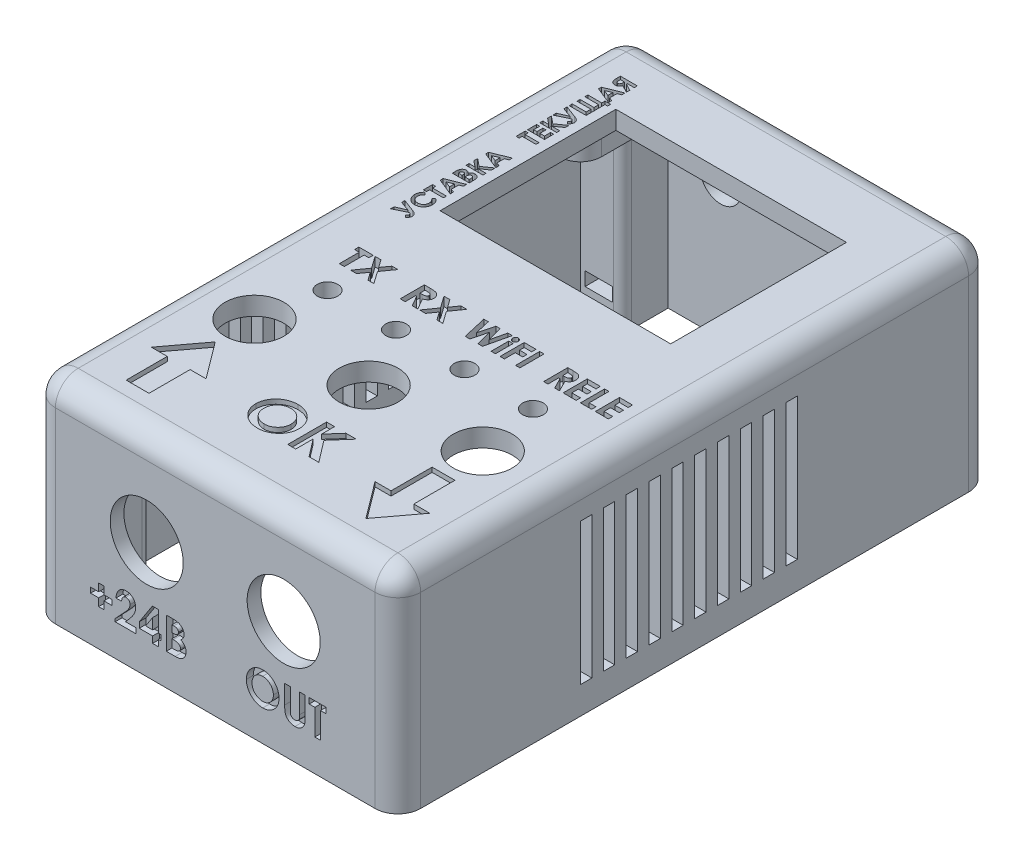
SolidWorks part; units mm, degrees
ref_plane "Спереди" through (0, 0, 0) normal (0, 0, 1) x (1, 0, 0)
ref_plane "Сверху" through (0, 0, 0) normal (0, 1, 0) x (1, 0, 0)
ref_plane "Справа" through (0, 0, 0) normal (1, 0, 0) x (0, 0, -1)
sketch "Эскиз1" plane through (0, 0, 0) normal (0, 1, 0) x (1, 0, 0)
  line L0 (-1000, 0) -> (49000, 0) construction
  line L1 (0, -1000) -> (0, 49000) construction
  line L2 (-1000, -65) -> (49000, -65) construction
  line L3 (-1000, 65) -> (49000, 65) construction
  line L4 (40, -1000) -> (40, 49000) construction
  line L5 (-40, -1000) -> (-40, 49000) construction
  line L6 (-40, 65) -> (40, 65)
  line L7 (40, 65) -> (40, -65)
  line L8 (40, -65) -> (-40, -65)
  line L9 (-40, -65) -> (-40, 65)
extrude "Бобышка-Вытянуть1" add sketch "Эскиз1" along normal blind 4
sketch "Эскиз2" plane through (0, 4, 0) normal (0, 1, 0) x (1, 0, 0)
  line L0 (-1040, 65) -> (48960, 65) construction
  line L1 (-1040, 48) -> (48960, 48) construction
  line L2 (-1040, 9.5) -> (48960, 9.5) construction
  line L3 (0, -1000) -> (0, 49000) construction
  line L4 (25.25, -1000) -> (25.25, 49000) construction
  line L5 (-25.25, -1000) -> (-25.25, 49000) construction
  line L6 (-25.25, 48) -> (25.25, 48)
  line L7 (25.25, 48) -> (25.25, 9.5)
  line L8 (25.25, 9.5) -> (-25.25, 9.5)
  line L9 (-25.25, 9.5) -> (-25.25, 48)
extrude "Вырез-Вытянуть1" cut sketch "Эскиз2" against normal blind 4
sketch "Эскиз3" plane through (0, 4, 0) normal (0, 1, 0) x (1, 0, 0)
  line L0 (-1025.25, 9.5) -> (48974.75, 9.5) construction
  line L1 (-1025.25, -32.9) -> (48974.75, -32.9) construction
  line L2 (0, -1000) -> (0, 49000) construction
  line L3 (25, -1000) -> (25, 49000) construction
  line L4 (-25, -1000) -> (-25, 49000) construction
  line L5 (-1025.25, -31.4) -> (48974.75, -31.4) construction
  circle A3 centre (-25, -31.4) radius 6.45
  circle A4 centre (0, -31.4) radius 6.45
  circle A5 centre (25, -31.4) radius 6.45
extrude "Вырез-Вытянуть2" cut sketch "Эскиз3" against normal blind 4
sketch "Эскиз4" plane through (0, 4, 0) normal (0, 1, 0) x (1, 0, 0)
  line L0 (-1025, -32.9) -> (48975, -32.9) construction
  line L1 (-1025, -17.9) -> (48975, -17.9) construction
  line L2 (0, -1032.9) -> (0, 48967.1) construction
  line L3 (7.5, -1032.9) -> (7.5, 48967.1) construction
  line L4 (-7.5, -1032.9) -> (-7.5, 48967.1) construction
  line L5 (-22.5, -1032.9) -> (-22.5, 48967.1) construction
  line L6 (22.5, -1032.9) -> (22.5, 48967.1) construction
  circle A0 centre (-7.5, -17.9) radius 2.25
  circle A1 centre (-22.5, -17.9) radius 2.25
  circle A2 centre (7.5, -17.9) radius 2.25
  circle A3 centre (22.5, -17.9) radius 2.25
extrude "Вырез-Вытянуть3" cut sketch "Эскиз4" against normal blind 4
sketch "Эскиз5" plane through (0, 0, 0) normal (0, -1, 0) x (1, 0, 0)
  line L0 (0, -1000) -> (0, 49000) construction
  line L1 (35, -1000) -> (35, 49000) construction
  line L2 (-35, -1000) -> (-35, 49000) construction
  line L3 (-1000, 0) -> (49000, 0) construction
  line L4 (-1000, -50) -> (49000, -50) construction
  line L5 (-1000, 50) -> (49000, 50) construction
  line L14 (-38, -1000) -> (-38, 49000) construction
  line L15 (38, -1000) -> (38, 49000) construction
  line L16 (-1000, 52) -> (49000, 52) construction
  line L17 (-1000, -52) -> (49000, -52) construction
  line L18 (-30, 40) -> (-38, 40)
  line L19 (-38, 40) -> (-38, 50)
  line L20 (-25, 45) -> (-25, 52)
  line L21 (-25, 52) -> (-38, 52)
  line L22 (-38, 52) -> (-38, 50)
  line L23 (30, 40) -> (38, 40)
  line L24 (38, 40) -> (38, 52)
  line L25 (38, 52) -> (25, 52)
  line L26 (25, 52) -> (25, 45)
  line L27 (-25.8, -45.4) -> (-25.8, -52)
  line L28 (-25.8, -52) -> (-38, -52)
  line L29 (-38, -52) -> (-38, -40.8)
  line L30 (-38, -40.8) -> (-30.4, -40.8)
  line L31 (30.4, -40.8) -> (38, -40.8)
  line L32 (38, -40.8) -> (38, -52)
  line L33 (38, -52) -> (25.8, -52)
  line L34 (25.8, -52) -> (25.8, -45.4)
  arc A0 (-30, 40) -> (-25, 45) centre (-30, 45) ccw
  arc A1 (25, 45) -> (30, 40) centre (30, 45) ccw
  arc A3 (-25.8, -45.4) -> (-30.4, -40.8) centre (-30.4, -45.4) ccw
  arc A4 (30.4, -40.8) -> (25.8, -45.4) centre (30.4, -45.4) ccw
  dimension "D1" = 3
  dimension "D2" = 3
  dimension "D3" = 2
  dimension "D4" = 2
extrude "Бобышка-Вытянуть2" add sketch "Эскиз5" along normal blind 4
sketch "Эскиз6" plane through (0, 0, 0) normal (0, -1, 0) x (1, 0, 0)
  line L0 (-1000, 0) -> (49000, 0) construction
  line L1 (0, -1000) -> (0, 49000) construction
  line L2 (35, -1000) -> (35, 49000) construction
  line L3 (-35, -1000) -> (-35, 49000) construction
  line L4 (-1000, -50) -> (49000, -50) construction
  line L5 (-1000, 50) -> (49000, 50) construction
  line L6 (-1040, 65) -> (48960, 65) construction
  line L7 (-1040, -65) -> (48960, -65) construction
  line L8 (-40, -935) -> (-40, 49065) construction
  line L9 (40, -935) -> (40, 49065) construction
  line L10 (-37, -62) -> (-37, 62)
  line L11 (-37, 62) -> (37, 62)
  line L12 (-37, -62) -> (37, -62)
  line L13 (37, -62) -> (37, 62)
  line L14 (-40, 65) -> (40, 65)
  line L15 (-37, -935) -> (-37, 49065) construction
  line L16 (-1040, -62) -> (48960, -62) construction
  line L17 (37, -935) -> (37, 49065) construction
  line L18 (-1040, 62) -> (48960, 62) construction
  line L19 (40, 65) -> (40, -65)
  line L20 (40, -65) -> (-40, -65)
  line L21 (-40, -65) -> (-40, 65)
  dimension "D1" = 3
extrude "Бобышка-Вытянуть3" add sketch "Эскиз6" along normal blind 42
fillet "Скругление2" radius 5 4 edges at (0, 4, 65) (40, 4, 0) (-40, 4, 0) (0, 4, -65)
fillet "Скругление3" radius 5 6 edges at (-38.5355, 2.5355, 63.5355) (38.5355, 2.5355, -63.5355) (-38.5355, 2.5355, -63.5355) (-40, -21.5, 65) (40, -21.5, -65) (-40, -21.5, -65)
fillet "Скругление4" radius 5 2 edges at (38.5355, 2.5355, 63.5355) (40, -21.5, 65)
sketch "Эскиз7" plane through (0, 0, 65) normal (0, 0, 1) x (1, 0, 0)
  line L0 (-1035, 4) -> (48965, 4) construction
  line L1 (-1040, -42) -> (48960, -42) construction
  line L2 (0, -1000) -> (0, 49000) construction
  line L3 (15, -1000) -> (15, 49000) construction
  line L4 (-15, -1000) -> (-15, 49000) construction
  line L5 (-1040, -16.5) -> (48960, -16.5) construction
  circle A0 centre (-15, -16.5) radius 8
  circle A1 centre (15, -16.5) radius 8
extrude "Вырез-Вытянуть4" cut sketch "Эскиз7" against normal blind 37
sketch "Эскиз8" plane through (0, 0, -65) normal (0, 0, -1) x (-1, 0, 0)
  line L0 (-1035, 4) -> (48965, 4) construction
  line L1 (-1040, -42) -> (48960, -42) construction
  line L2 (-40, -1037) -> (-40, 48963) construction
  line L3 (40, -1037) -> (40, 48963) construction
  line L4 (-1035, -12) -> (48965, -12) construction
  line L5 (0, -1000) -> (0, 49000) construction
  line L6 (16.3, -1000) -> (16.3, 49000) construction
  circle A0 centre (16.3, -12) radius 4.5
  dimension "D1" = 16
extrude "Вырез-Вытянуть5" cut sketch "Эскиз8" against normal blind 37
sketch "Эскиз9" plane through (0, 4, 0) normal (0, 1, 0) x (1, 0, 0)
  line L0 (-1017.9464, -57) -> (48982.0536, -57) construction
  line L1 (-25, -1032.9) -> (-25, 48967.1) construction
  line L2 (25, -1032.9) -> (25, 48967.1) construction
  line L3 (-1017.9464, -40) -> (48982.0536, -40) construction
  line L4 (-19, -1032.9) -> (-19, 48967.1) construction
  line L5 (-31, -1032.9) -> (-31, 48967.1) construction
  line L6 (-1017.9464, -48) -> (48982.0536, -48) construction
  line L7 (-22.5, -1032.9) -> (-22.5, 48967.1) construction
  line L8 (-27.5, -1032.9) -> (-27.5, 48967.1) construction
  line L9 (-25, -40) -> (-31, -48)
  line L10 (-31, -48) -> (-27.5, -48)
  line L11 (-27.5, -48) -> (-27.5, -57)
  line L12 (-27.5, -57) -> (-22.5, -57)
  line L13 (-22.5, -57) -> (-22.5, -48)
  line L14 (-22.5, -48) -> (-19, -48)
  line L15 (-19, -48) -> (-25, -40)
  line L16 (31, -1032.9) -> (31, 48967.1) construction
  line L17 (19, -1032.9) -> (19, 48967.1) construction
  line L18 (27.5, -1032.9) -> (27.5, 48967.1) construction
  line L19 (22.5, -1032.9) -> (22.5, 48967.1) construction
  line L20 (-1017.9464, -49) -> (48982.0536, -49) construction
  line L21 (25, -57) -> (19, -49)
  line L22 (25, -57) -> (31, -49)
  line L23 (19, -49) -> (22.5, -49)
  line L24 (22.5, -49) -> (22.5, -40)
  line L25 (22.5, -40) -> (27.5, -40)
  line L26 (27.5, -40) -> (27.5, -49)
  line L27 (27.5, -49) -> (31, -49)
  text T0 "<b>ОК</b>" font "Century Gothic" height 8.5
extrude "Вырез-Вытянуть6" cut sketch "Эскиз9" against normal blind 1
sketch "Эскиз10" plane through (-40, 0, 0) normal (-1, 0, 0) x (0, 0, 1)
  line L0 (-1065, -42) -> (48935, -42) construction
  line L1 (-1065, -1) -> (48935, -1) construction
  line L2 (0, -1000) -> (0, 49000) construction
  line L3 (25, -1000) -> (25, 49000) construction
  line L4 (-25, -1000) -> (-25, 49000) construction
  line L5 (25, -1000) -> (25, 49000) construction
  line L6 (-25, -1000) -> (-25, 49000) construction
  line L7 (-1065, -19) -> (48935, -19) construction
  line L8 (-22.5, -33) -> (-22.5, -36)
  line L9 (-1065, -5) -> (48935, -5) construction
  line L10 (-22.5, -36) -> (-20, -36)
  line L11 (-22.5, -5) -> (-22.5, -33)
  line L12 (-20, -5) -> (-20, -33)
  line L13 (-17.5, -5) -> (-17.5, -33)
  line L14 (-15, -5) -> (-15, -33)
  line L15 (-12.5, -5) -> (-12.5, -33)
  line L16 (-10, -5) -> (-10, -33)
  line L17 (-7.5, -5) -> (-7.5, -33)
  line L18 (-5, -5) -> (-5, -33)
  line L19 (-2.5, -5) -> (-2.5, -33)
  line L20 (0, -5) -> (0, -33)
  line L21 (2.5, -5) -> (2.5, -33)
  line L22 (5, -5) -> (5, -33)
  line L23 (7.5, -5) -> (7.5, -33)
  line L24 (10, -5) -> (10, -33)
  line L25 (12.5, -5) -> (12.5, -33)
  line L26 (15, -5) -> (15, -33)
  line L27 (17.5, -5) -> (17.5, -33)
  line L28 (20, -5) -> (20, -33)
  line L29 (22.5, -5) -> (22.5, -33)
  line L30 (25, -5) -> (25, -33)
  line L32 (25, -5) -> (22.5, -5)
  line L33 (20, -5) -> (17.5, -5)
  line L36 (15, -5) -> (12.5, -5)
  line L37 (10, -5) -> (7.5, -5)
  line L40 (2.5, -5) -> (5, -5)
  line L41 (0, -5) -> (-2.5, -5)
  line L44 (-7.5, -5) -> (-5, -5)
  line L45 (-10, -5) -> (-12.5, -5)
  line L48 (-17.5, -5) -> (-15, -5)
  line L49 (-20, -5) -> (-22.5, -5)
  line L51 (-20, -36) -> (-20, -33)
  line L52 (-12.5, -36) -> (-10, -36)
  line L53 (-17.5, -33) -> (-17.5, -36)
  line L54 (-2.5, -36) -> (0, -36)
  line L55 (-15, -36) -> (-15, -33)
  line L56 (7.5, -36) -> (10, -36)
  line L57 (-12.5, -33) -> (-12.5, -36)
  line L58 (17.5, -36) -> (20, -36)
  line L59 (-10, -36) -> (-10, -33)
  line L60 (-7.5, -33) -> (-7.5, -36)
  line L61 (-15, -36) -> (-17.5, -36)
  line L62 (-5, -36) -> (-5, -33)
  line L63 (-5, -36) -> (-7.5, -36)
  line L64 (-2.5, -33) -> (-2.5, -36)
  line L65 (5, -36) -> (2.5, -36)
  line L66 (0, -36) -> (0, -33)
  line L67 (15, -36) -> (12.5, -36)
  line L68 (2.5, -33) -> (2.5, -36)
  line L69 (25, -36) -> (22.5, -36)
  line L70 (5, -36) -> (5, -33)
  line L71 (7.5, -33) -> (7.5, -36)
  line L72 (10, -33) -> (10, -36)
  line L73 (12.5, -33) -> (12.5, -36)
  line L74 (15, -33) -> (15, -36)
  line L75 (17.5, -33) -> (17.5, -36)
  line L76 (20, -33) -> (20, -36)
  line L77 (22.5, -33) -> (22.5, -36)
  line L78 (25, -33) -> (25, -36)
extrude "Вырез-Вытянуть7" cut sketch "Эскиз10" against normal blind 98
sketch "Эскиз11" plane through (0, 4, 0) normal (0, 1, 0) x (1, 0, 0)
  line L0 (-1023.7157, -11.5684) -> (48976.2843, -11.5684) construction
  line L1 (-27.3306, -993.2758) -> (-27.3306, 49006.7242) construction
  text T0 "<b>TX</b>" font "Century Gothic" height in points 20
  text T1 "<b>RX</b>" font "Century Gothic" height in points 20
  text T2 "<b>WiFI</b>" font "Century Gothic" height in points 20
  text T3 "<b>RELE</b>" font "Century Gothic" height in points 20
  text T4 "<b>УСТАВКА</b>" font "Century Gothic" height in points 14
  text T5 "<b>   ТЕКУЩАЯ</b>" font "Century Gothic" height in points 14
extrude "Вырез-Вытянуть8" cut sketch "Эскиз11" against normal blind 2
sketch "Эскиз12" plane through (0, 0, 65) normal (0, 0, 1) x (1, 0, 0)
  text T0 "<b>+24В</b>" font "Century Gothic" height in points 26
  text T1 "<b>OUT</b>" font "Century Gothic" height in points 26
extrude "Вырез-Вытянуть9" cut sketch "Эскиз12" against normal blind 1.5
ref_plane "Плоскость1" through (0, -2, 0) normal (0, -1, 0) x (-1, 0, 0)
sketch "Эскиз14" plane through (0, -4, 0) normal (0, -1, 0) x (1, 0, 0)
  line L0 (0, -1000) -> (0, 49000) construction
  line L1 (-1000, 0) -> (49000, 0) construction
  line L2 (-1000, -50) -> (49000, -50) construction
  line L3 (-1000, 50) -> (49000, 50) construction
  line L4 (35, -1000) -> (35, 49000) construction
  line L5 (-35, -1000) -> (-35, 49000) construction
  line L6 (-32, -1000) -> (-32, 49000) construction
  line L7 (-1000, 47) -> (49000, 47) construction
  line L8 (32, -1000) -> (32, 49000) construction
  line L9 (-1000, -47) -> (49000, -47) construction
  circle A0 centre (-32, 47) radius 1.5
  circle A1 centre (32, 47) radius 1.5
  circle A2 centre (32, -47) radius 1.5
  circle A3 centre (-32, -47) radius 1.5
sketch "Эскиз16" plane through (0, -2, 0) normal (0, -1, 0) x (1, 0, 0)
  line L0 (-32, -1047) -> (-32, 48953) construction
  line L25 (-25, -948) -> (-25, 49052) construction
  line L26 (25, -948) -> (25, 49052) construction
  line L27 (32, -953) -> (32, 49047) construction
  line L35 (-29.0031, -48.7302) -> (-29.0031, -45.2698)
  line L38 (-34.9969, -45.2698) -> (-34.9969, -48.7302)
  line L40 (22, -948) -> (22, 49052) construction
  line L41 (-22, -948) -> (-22, 49052) construction
  line L42 (-1025, 52) -> (48975, 52) construction
  line L50 (34.9969, -48.7302) -> (34.9969, -45.2698)
  line L53 (29.0031, -45.2698) -> (29.0031, -48.7302)
  line L55 (-1025.8, -52) -> (48974.2, -52) construction
  line L56 (-1025, 56) -> (48975, 56) construction
  line L57 (-1025.8, -56) -> (48974.2, -56) construction
  line L70 (-1032, 44) -> (48968, 44) construction
  line L71 (-30.2678, 50) -> (-22, 50)
  line L72 (-33.7322, 44) -> (-30.268, 43.9999)
  line L73 (30.2691, 44) -> (33.7326, 44.001)
  line L74 (33.7326, 44.001) -> (35.4635, 47.001)
  line L75 (29.0031, -48.7302) -> (32, -50.4605) [skipped]
  line L76 (32, -50.4605) -> (34.9969, -48.7302) [skipped]
  line L77 (-34.9969, -48.7302) -> (-32, -50.4605) [skipped]
  line L78 (-32, -50.4605) -> (-29.0031, -48.7302) [skipped]
  line L81 (-30.2678, 50) -> (-33.732, 50.0001)
  line L82 (-33.732, 50.0001) -> (-35.4642, 47.0001)
  line L83 (-35.4642, 47.0001) -> (-33.7322, 44)
  line L84 (35.4635, 47.001) -> (33.7309, 50)
  line L85 (33.7309, 50) -> (30.2674, 49.999)
  line L88 (-22, 50) -> (-22, 44)
  line L89 (-22, 44) -> (-30.268, 43.9999)
  line L90 (-28.5358, 46.9999) -> (-30.2678, 50) [skipped]
  line L91 (-30.268, 43.9999) -> (-28.5358, 46.9999) [skipped]
  line L92 (30.2674, 49.999) -> (28.5365, 46.999) [skipped]
  line L93 (28.5365, 46.999) -> (30.2691, 44) [skipped]
  line L94 (30.2674, 49.999) -> (22, 49.999)
  line L95 (22, 49.999) -> (22, 44)
  line L96 (22, 44) -> (30.2691, 44)
  line L97 (-1037, -40.8) -> (48963, -40.8) construction
  line L98 (-1037, -37.8) -> (48963, -37.8) construction
  line L99 (-34.9969, -48.7302) -> (43221.0407, -25126.9122) construction
  line L100 (-29.0031, -48.7302) -> (-43345.0118, -25023.185) construction
  line L101 (34.9969, -48.7302) -> (-43224.0961, -25121.6415) construction
  line L102 (29.0031, -48.7302) -> (43324.211, -25059.2275) construction
  line L103 (-32, -43.5395) -> (-34.9969, -45.2698) [skipped]
  line L104 (-29.0031, -45.2698) -> (-32, -43.5395) [skipped]
  line L105 (-34.9969, -48.7302) -> (-32, -50.4581)
  line L106 (-32, -50.4581) -> (-29.0031, -48.7302)
  line L107 (-29.0031, -45.2698) -> (-29.0031, -37.8)
  line L108 (-29.0031, -37.8) -> (-34.9969, -37.8)
  line L109 (-34.9969, -37.8) -> (-34.9969, -45.2698)
  line L110 (34.9969, -45.2698) -> (34.9969, -37.8)
  line L111 (34.9969, -37.8) -> (29.0031, -37.8)
  line L112 (29.0031, -37.8) -> (29.0031, -45.2698)
  line L113 (29.0031, -48.7302) -> (32, -50.4672)
  line L114 (32, -43.5395) -> (29.0031, -45.2698) [skipped]
  line L115 (34.9969, -45.2698) -> (32, -43.5395) [skipped]
  line L116 (32, -50.4672) -> (34.9969, -48.7302)
  circle A0 centre (-32, 47) radius 3 construction
  circle A1 centre (32, 47) radius 3 construction
  circle A2 centre (32, -47) radius 3 construction
  circle A3 centre (-32, -47) radius 3 construction
  circle A4 centre (-32, 47) radius 3.0001 construction
  circle A5 centre (-32, -47) radius 2.9969 construction
  circle A6 centre (32, 47) radius 2.9995 construction
  circle A7 centre (32, -47) radius 2.9969 construction
  dimension "D1" = 4
  dimension "D2" = 4
  dimension "D3" = 3
  dimension "D4" = 3
  dimension "D5" = 3
sketch "Эскиз17" plane through (0, 0, 0) normal (0, -1, 0) x (1, 0, 0)
  line L0 (-1025.25, -9.5) -> (48974.75, -9.5) construction
  line L1 (-1025.25, 5.5) -> (48974.75, 5.5) construction
  line L2 (-33.5521, -1002.0408) -> (-33.5521, 48997.9592) construction
  line L3 (-13.5521, -1002.0408) -> (-13.5521, 48997.9592) construction
  line L4 (-13.5521, -9.5) -> (-33.5521, -9.5)
  line L5 (-33.5521, -9.5) -> (-33.5521, 5.5)
  line L6 (-33.5521, 5.5) -> (-13.5521, 5.5)
  line L7 (-13.5521, 5.5) -> (-13.5521, -9.5)
extrude "Вырез-Вытянуть12" cut sketch "Эскиз17" against normal blind 1
sketch "Эскиз18" plane through (0, 0, -65) normal (0, 0, -1) x (-1, 0, 0)
  line L0 (-1018.6835, -20.052) -> (48981.3165, -20.052) construction
  line L1 (-24.5058, -1017.2424) -> (-24.5058, 48982.7576) construction
  line L2 (-19.5058, -1017.2424) -> (-19.5058, 48982.7576) construction
  line L3 (-1018.6835, -18.552) -> (48981.3165, -18.552) construction
  line L4 (-24.5058, -18.552) -> (-24.5058, -20.052)
  line L5 (-24.5058, -20.052) -> (-19.5058, -20.052)
  line L6 (-19.5058, -20.052) -> (-19.5058, -18.552)
  arc A0 (-24.5058, -18.552) -> (-19.5058, -18.552) centre (-22.0058, -18.552) cw
  dimension "D1" = 5
  dimension "D2" = 1.5
extrude "Вырез-Вытянуть13" cut sketch "Эскиз18" against normal blind 15
sketch "Эскиз19" plane through (0, 0, 0) normal (0, -1, 0) x (1, 0, 0)
  line L0 (-1025, 52) -> (48975, 52) construction
  line L1 (-25, -948) -> (-25, 49052) construction
  line L2 (25, -948) -> (25, 49052) construction
  line L3 (-1025.8, -52) -> (48974.2, -52) construction
  line L5 (-37.4635, 52) -> (-37.4635, 62.6639)
  line L6 (-37.4635, 62.6639) -> (-27, 62.6639)
  line L9 (37.7861, 52) -> (37.7861, 62.6639)
  line L10 (37.7861, 62.6639) -> (27, 62.6639)
  line L14 (37.7861, -62.7685) -> (37.7861, -52)
  line L18 (-37.4635, -62.7685) -> (-37.4635, -52)
  line L20 (-25.8, -1052) -> (-25.8, 48948) construction
  line L21 (25.8, -1052) -> (25.8, 48948) construction
  line L22 (-37.4635, -52) -> (-27.8, -52)
  line L24 (-27.8, -62.7685) -> (-37.4635, -62.7685)
  line L25 (37.7861, -52) -> (27.8, -52)
  line L27 (27.8, -62.7685) -> (37.7861, -62.7685)
  line L28 (-27, 62.6639) -> (-27, 52)
  line L29 (27, 62.6639) -> (27, 52)
  line L30 (27.8, -52) -> (27.8, -62.7685)
  line L31 (-27.8, -52) -> (-27.8, -62.7685)
  line L32 (27, 52) -> (37.7861, 52)
  line L33 (-27, 52) -> (-37.4635, 52)
extrude "Бобышка-Вытянуть4" add sketch "Эскиз19" along normal blind 42
sketch "Эскиз20" plane through (0, -42, 0) normal (0, -1, 0) x (1, 0, 0)
  line L0 (-1033.5639, 52) -> (48966.4361, 52) construction
  line L1 (0, -201000) -> (0, 249000) construction
  line L2 (-1027.7435, -52) -> (48972.2565, -52) construction
  line L3 (-32, -201000) -> (-32, 249000) construction
  line L4 (25.8, -1062) -> (25.8, 48938) construction
  line L5 (-25.8, -1062) -> (-25.8, 48938) construction
  line L6 (-1018.5579, 65) -> (48981.4421, 65) construction
  line L8 (-1018.7347, -65) -> (48981.2653, -65) construction
  line L10 (-1033.5639, 58.5) -> (48966.4361, 58.5) construction
  line L11 (-1027.7435, -58.5) -> (48972.2565, -58.5) construction
  line L12 (40, -1018.7265) -> (40, 48981.2735) construction
  line L14 (-40, -1003.4152) -> (-40, 48996.5848) construction
  line L16 (-33, -1003.4152) -> (-33, 48996.5848) construction
  line L17 (33, -1018.7265) -> (33, 48981.2735) construction
  circle A0 centre (-33, 58.5) radius 1.5
  circle A1 centre (33, 58.5) radius 1.5
  circle A2 centre (33, -58.5) radius 1.5
  circle A3 centre (-33, -58.5) radius 1.5
extrude "Вырез-Вытянуть14" cut sketch "Эскиз20" against normal blind 24
ref_plane "Плоскость2" through (0, -37, 0) normal (0, -1, 0) x (-1, 0, 0)
sketch "Эскиз21" plane through (0, -37, 0) normal (0, -1, 0) x (-1, 0, 0)
  line L0 (-36.6994, 50.7861) -> (-29.3006, 50.7861)
  line L2 (-29.3006, 56.3641) -> (-29.3006, 60.6359)
  line L3 (-29.3006, 60.6359) -> (-33, 62.7717)
  line L4 (-33, 62.7717) -> (-36.6994, 60.6359)
  line L5 (-36.6994, 60.6359) -> (-36.6994, 56.3641)
  line L8 (36, 56.7679) -> (36, 60.2321)
  line L9 (36, 60.2321) -> (33, 61.9641)
  line L10 (33, 61.9641) -> (30, 60.2321)
  line L11 (30, 60.2321) -> (30, 56.7679)
  line L14 (30, -56.7679) -> (30, -60.2321)
  line L15 (30, -60.2321) -> (33, -61.9641)
  line L16 (33, -61.9641) -> (36, -60.2321)
  line L17 (36, -60.2321) -> (36, -56.7679)
  line L20 (-36, -56.7679) -> (-36, -60.2321)
  line L21 (-36, -60.2321) -> (-33, -61.9641)
  line L22 (-33, -61.9641) -> (-30, -60.2321)
  line L23 (-30, -60.2321) -> (-30, -56.7679)
  line L25 (-29.3006, 50.7861) -> (-29.3006, 56.3641)
  line L26 (-36.6994, 50.7861) -> (-36.6994, 56.3641)
  line L27 (30, 56.7679) -> (30, 51.278)
  line L28 (-36.6994, 56.3641) -> (-33, 54.2283) [skipped]
  line L29 (-33, 54.2283) -> (-29.3006, 56.3641) [skipped]
  line L30 (30, 56.7679) -> (33, 55.0359) [skipped]
  line L31 (33, 55.0359) -> (36, 56.7679) [skipped]
  line L32 (30, 51.278) -> (36, 51.278)
  line L33 (36, 51.278) -> (36, 56.7679)
  line L34 (30, -56.7679) -> (30, -50.5394)
  line L35 (33, -55.0359) -> (30, -56.7679) [skipped]
  line L36 (36, -56.7679) -> (33, -55.0359) [skipped]
  line L37 (-30, -56.7679) -> (-33, -55.0359) [skipped]
  line L38 (-33, -55.0359) -> (-36, -56.7679) [skipped]
  line L39 (30, -50.5394) -> (36, -50.5394)
  line L40 (36, -50.5394) -> (36, -56.7679)
  line L41 (-36, -56.7679) -> (-36, -50.5394)
  line L42 (-36, -50.5394) -> (-30, -50.5394)
  line L43 (-30, -50.5394) -> (-30, -56.7679)
  circle A0 centre (-33, 58.5) radius 3.6994 construction
  circle A1 centre (33, 58.5) radius 3 construction
  circle A2 centre (33, -58.5) radius 3 construction
  circle A3 centre (-33, -58.5) radius 3 construction
extrude "Вырез-Вытянуть15" cut sketch "Эскиз21" against normal blind 3
fillet "Скругление5" radius 2 4 edges at (27, -23, 52) (-27, -23, 52) (27.8, -23, -52) (-27.8, -23, -52)
